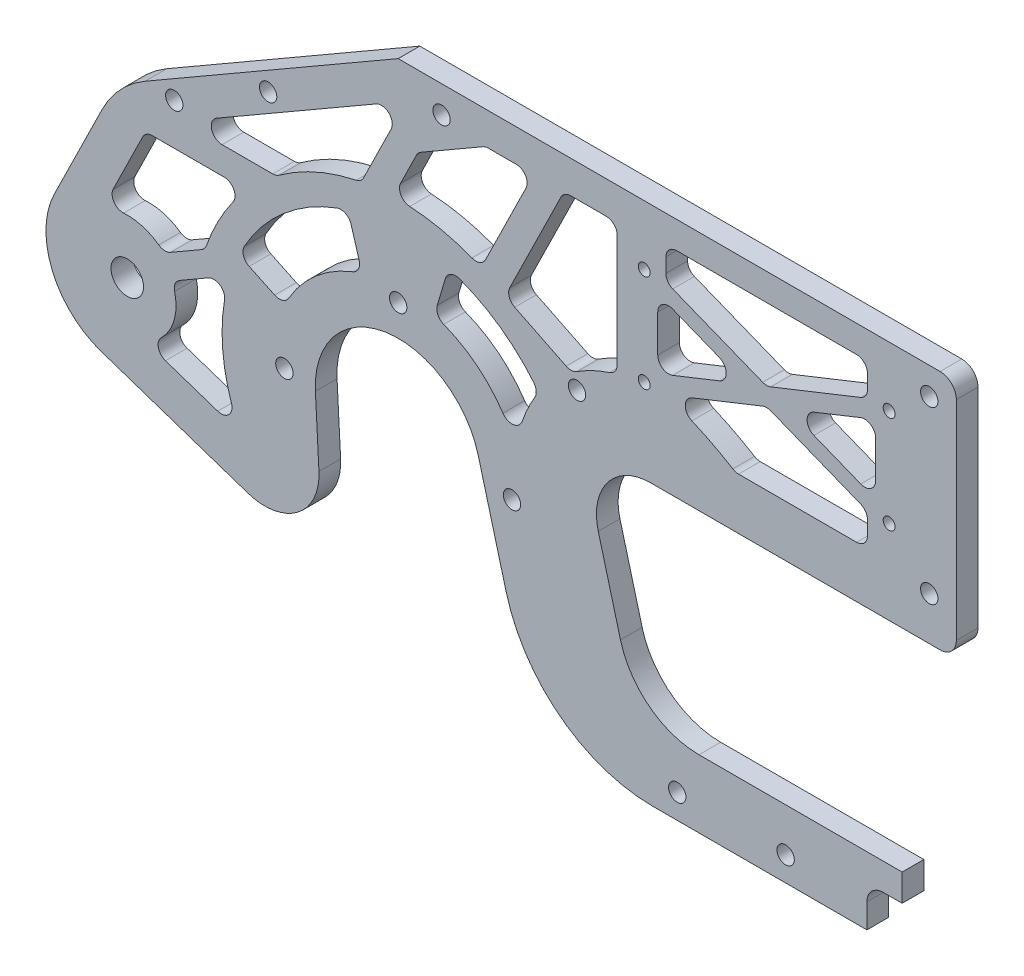
SolidWorks part; units mm, degrees
material "环氧树脂FR-4"
ref_plane "前视基准面" through (0, 0, 0) normal (0, 0, 1) x (1, 0, 0)
ref_plane "上视基准面" through (0, 0, 0) normal (0, 1, 0) x (1, 0, 0)
ref_plane "右视基准面" through (0, 0, 0) normal (1, 0, 0) x (0, 0, -1)
sketch "草图1" plane through (0, 0, 0) normal (0, 0, 1) x (1, 0, 0)
  line L1 (0, 60) -> (103, 60)
  line L2 (103, 60) -> (103, 15.5)
  line L3 (103, 15.5) -> (33.55, 15.5)
  line L4 (33.55, 15.5) -> (44, -23.5)
  line L5 (44, -23.5) -> (93, -23.5)
  line L6 (93, -23.5) -> (93, -36)
  line L7 (93, -36) -> (10, -36)
  line L9 (-50, 0) -> (0, 0) construction
  line L10 (0, 60) -> (-51.9615, 30)
  line L11 (10, -36) -> (-54.7807, -14.2178)
  line L12 (-51.9615, 30) -> (-63.4602, 6.6199)
  circle A0 centre (0, 0) radius 15.3
  circle A1 centre (0, 0) radius 20 construction
  circle A2 centre (-50, 0) radius 3
  circle A3 centre (-50, 0) radius 15
  dimension "D1" = 30.6
  dimension "D2" = 40
  dimension "D13" = 50
  dimension "D14" = 6
  dimension "D8" = 93
  dimension "D6" = 30
  dimension "D3" = 36
  dimension "D4" = 105
  dimension "D5" = 44.5
  dimension "D7" = 10
  dimension "D9" = 39
  dimension "D10" = 153
  dimension "D11" = 0
  dimension "D12" = 60
  dimension "D16" = 44
  dimension "D17" = 30
  dimension "D18" = 30
extrude "凸台-拉伸1" add sketch "草图1" along normal blind 4 contours A3 L11 L7 L6 L5 L4 L3 L2 L1 A0 | A3 A2 region at (25.8343, 17.652, 0) region at (-46.6978, 14.1967, 0)
sketch "草图4" plane through (0, 0, 0) normal (0, 0, 1) x (1, 0, 0)
  circle A0 centre (0, 0) radius 34
  dimension "D1" = 68
sketch "草图2" plane through (0, 0, 0) normal (0, 0, 1) x (1, 0, 0)
  line L0 (0, 0) -> (0, 21) construction
  circle A0 centre (0, 21) radius 1.6
  circle A1 centre (21, 0) radius 1.6
  circle A2 centre (0, -21) radius 1.6
  circle A3 centre (-21, 0) radius 1.6
  dimension "D3" = 3.2
  dimension "D2" = 21
  dimension "D1" = 4
extrude "切除-拉伸1" cut sketch "草图2" along normal through all
fillet "圆角1" radius 10 1 edges at (33.55, 15.5, 2)
fillet "圆角2" radius 15 1 edges at (44, -23.5, 2)
sketch "草图3" plane through (0, 0, 0) normal (0, 0, 1) x (1, 0, 0)
  line L1 (90.6, 31) -> (45.4, 31) construction
  line L2 (90.6, 31) -> (90.6, 49) construction
  line L3 (90.6, 49) -> (45.4, 49) construction
  line L4 (45.4, 31) -> (45.4, 49) construction
  line L5 (90.6, 31) -> (45.4, 49) construction
  line L6 (90.6, 49) -> (45.4, 31) construction
  circle A0 centre (90.6, 49) radius 1.1
  circle A1 centre (45.4, 49) radius 1.1
  circle A2 centre (45.4, 31) radius 1.1
  circle A3 centre (90.6, 31) radius 1.1
  point P0 (68, 40)
  dimension "D5" = 2.2
  dimension "D1" = 45.2
  dimension "D2" = 18
  dimension "D3" = 40
  dimension "D4" = 68
extrude "切除-拉伸2" cut sketch "草图3" along normal through all
sketch "草图5" plane through (0, 0, 4) normal (0, 0, 1) x (1, 0, 0)
  line L0 (10, -36) -> (-54.7807, -14.2178) construction
  circle A0 centre (-35, -20.8689) radius 12.5
  circle A1 centre (-50, 0) radius 3 construction
  dimension "D1" = 15
  dimension "D2" = 25
extrude "切除-拉伸3" [suppressed] cut sketch "草图5" against normal through all
sketch "草图7" plane through (0, 0, 4) normal (0, 0, 1) x (1, 0, 0)
  line L1 (14.7787, 3.9599) -> (25.4859, -36)
  line L5 (93, -36) -> (10, -36) construction
  line L6 (36.923, 2.9118) -> (41.021, -12.3823) construction
  line L8 (10, -36) -> (-54.7807, -14.2178) construction
  line L9 (14.7787, 3.9599) -> (-14.7787, -3.9599) construction
  line L11 (-13.8547, -27.979) -> (10, -36)
  line L12 (10, -36) -> (25.4859, -36)
  line L13 (-13.8547, -27.979) -> (-15.279, -0.8007)
  line L14 (-15.279, -0.8007) -> (14.7787, 3.9599)
  circle A0 centre (0, 0) radius 15.3 construction
  circle A1 centre (0, 0) radius 15.3 construction
  dimension "D1" = 12
extrude "切除-拉伸4" cut sketch "草图7" against normal through all
sketch "草图8" plane through (0, 0, 4) normal (0, 0, 1) x (1, 0, 0)
  line L0 (51.5, -31.5) -> (71.5, -31.5) construction
  line L3 (93, -23.5) -> (93, -36) construction
  line L9 (55.5099, -23.5) -> (93, -23.5) construction
  circle A4 centre (71.5, -31.5) radius 1.6
  circle A5 centre (51.5, -31.5) radius 1.6
  dimension "D1" = 8
  dimension "D2" = 3.2
  dimension "D3" = 21.5
  dimension "D4" = 20
extrude "切除-拉伸7" cut sketch "草图8" against normal through all
sketch "草图10" plane through (0, 0, 4) normal (0, 0, 1) x (1, 0, 0)
  line L0 (93, -28.5) -> (86.5, -28.5)
  line L1 (93, -23.5) -> (93, -36) construction
  line L2 (86.5, -28.5) -> (86.5, -36)
  line L3 (93, -36) -> (25.4859, -36) construction
  line L4 (86.5, -36) -> (93, -36)
  line L5 (93, -36) -> (93, -28.5)
  line L6 (55.5099, -23.5) -> (93, -23.5) construction
  dimension "D1" = 5
  dimension "D2" = 6.5
extrude "切除-拉伸8" cut sketch "草图10" against normal through all
sketch "草图17" plane through (0, 0, 0) normal (0, 0, -1) x (-1, 0, 0)
  line L0 (-103, 60) -> (-103, 15.5) construction
  line L1 (-103, 15.5) -> (-46.5822, 15.5) construction
  line L2 (0, 60) -> (-103, 60) construction
  circle A0 centre (-98, 23.5) radius 1.6
  circle A1 centre (-98, 55) radius 1.6
  circle A2 centre (-33, 23.5) radius 1.6
  circle A3 centre (-8, 55) radius 1.6
  dimension "D1" = 5
  dimension "D3" = 3.2
  dimension "D4" = 5
  dimension "D5" = 65
  dimension "D6" = 90
  dimension "D2" = 8
extrude "切除-拉伸14" cut sketch "草图17" against normal through all
fillet "圆角3" radius 3 1 edges at (86.5, -28.5, 2)
sketch "草图11" plane through (0, 0, 0) normal (0, 0, -1) x (-1, 0, 0)
  line L0 (-21.9089, -7) -> (-31.2966, -7)
  line L1 (-31.2966, -7) -> (-37.4595, -30)
  line L2 (-37.4595, -30) -> (-10, -30)
  line L3 (-10, -30) -> (-3.2852, -27.7422)
  line L4 (13.8547, -27.979) -> (54.7807, -14.2178) construction
  line L5 (-86.5, -36) -> (-25.4859, -36) construction
  line L6 (-36.923, 2.9118) -> (-41.021, -12.3823) construction
  line L7 (16, -19.8725) -> (43.4459, -10.6439)
  line L8 (16, -19.8725) -> (16, -16.5227)
  line L9 (28.5, 0) -> (37.5, 0)
  line L10 (47.3524, 28.0423) -> (-7.1185, 59.4911)
  line L11 (-7.1185, 59.4911) -> (-7.1185, 21.8707)
  line L12 (47.3524, 28.0423) -> (55.6635, 11.1434)
  line L13 (31.7893, 37.0277) -> (44.4834, 11.2168)
  line L14 (44.4834, 11.2168) -> (20.0794, 11.2168)
  line L15 (0, 60) -> (51.9615, 30) construction
  line L16 (26.3422, 40.1725) -> (40.583, 11.2168)
  line L17 (12.3354, 48.2594) -> (30.5534, 11.2168)
  line L18 (6.8883, 51.4042) -> (26.653, 11.2168)
  line L19 (-7.1185, 59.4911) -> (11.843, 20.9369)
  line L20 (50, 12.5) -> (4.9656, 22.4576)
  line L21 (51.9615, 30) -> (63.4602, 6.6199) construction
  line L22 (-20.0278, -11.3087) -> (-25.0361, -30)
  line L23 (-17.0059, -15.4855) -> (-20.895, -30)
  circle A0 centre (0, 0) radius 23
  circle A1 centre (0, -21) radius 7.5
  circle A2 centre (50, 0) radius 12.5
  circle A3 centre (21, 0) radius 7.5
  point P30 (0, -21)
  dimension "D1" = 15
  dimension "D5" = 25
  dimension "D8" = 46
  dimension "D2" = 6
  dimension "D3" = 8
  dimension "D4" = 7
  dimension "D6" = 7
  dimension "D7" = 16
  dimension "D9" = 4
  dimension "D10" = 5
  dimension "D11" = 3.5
  dimension "D12" = 3.5
  dimension "D13" = 9
  dimension "D14" = 9
  dimension "D15" = 12
  dimension "D16" = 4
extrude "切除-拉伸9" [suppressed] cut sketch "草图11" against normal through all contours A3 A0 L8 L7 A2 L9 | A2 L12 L10 L13 L20 | L20 L16 L10 L17 | L20 L18 L10 L19 | A0 L0 L1 L2 L22 | A1 A0 L23 L2 L3
fillet "圆角4" [suppressed] radius 3
sketch "草图12" [suppressed] plane through (0, 0, 0) normal (0, 0, -1) x (-1, 0, 0)
  line L0 (-4.0881, 42) -> (-10.4817, 55)
  line L1 (-10.4817, 55) -> (-28.4817, 55)
  line L2 (-28.4817, 55) -> (-22.0881, 42)
  line L3 (-22.0881, 42) -> (-4.0881, 42)
  line L4 (0, 60) -> (-103, 60) construction
  line L7 (-2.7623, 50.6337) -> (11.843, 20.9369) construction
  line L8 (-14.2191, 26) -> (3.7809, 26)
  line L9 (3.7809, 26) -> (-2.6127, 39)
  line L10 (-2.6127, 39) -> (-20.6127, 39)
  line L11 (-20.6127, 39) -> (-14.2191, 26)
  dimension "D6" = 3
  dimension "D1" = 5
  dimension "D2" = 5
  dimension "D3" = 18
  dimension "D4" = 13
  dimension "D5" = 2
extrude "切除-拉伸10" [suppressed] cut sketch "草图12" against normal blind 10 contours L2 L3 L0 L1 | L10 L11 L8 L9 | L8 L9 L10 L11
sketch "草图14" plane through (0, 0, 0) normal (0, 0, -1) x (-1, 0, 0)
  line L0 (0, 60) -> (-103, 60) construction
  line L1 (-103, 60) -> (-103, 15.5) construction
  circle A0 centre (-98, 55) radius 1.6
  circle A1 centre (-6, 55) radius 1.6
  dimension "D1" = 3.2
  dimension "D2" = 5
  dimension "D4" = 5
  dimension "D5" = 92
  dimension "D3" = 5
extrude "切除-拉伸11" [suppressed] cut sketch "草图14" against normal through all
chamfer "倒角1" [suppressed] distance 8 angle 45
sketch "草图15" [suppressed] plane through (0, 0, 0) normal (0, 0, -1) x (-1, 0, 0)
  line L0 (-26.1097, 7) -> (-21.9089, 7)
  line L1 (-15.404, 17.0797) -> (-22.2502, 31)
  line L2 (-22.2502, 31) -> (-40.4, 31)
  line L3 (-45.4, 31) -> (-42.7797, 25.6721)
  line L4 (-20.6127, 39) -> (-14.2191, 26) construction
  line L6 (-22.2502, 31) -> (-37.0907, 23.7012)
  circle A1 centre (0, 0) radius 23
  circle A2 centre (-46.5822, 5.5) radius 20.5274
  circle A4 centre (-45.4, 31) radius 5
  circle A5 centre (-21, 0) radius 1.6 construction
  dimension "D2" = 10
  dimension "D4" = 46
  dimension "D5" = 7
  dimension "D3" = 5
extrude "切除-拉伸12" [suppressed] cut sketch "草图15" against normal through all contours A4 L3 A2 L0 A1 L1 L2
sketch "草图16" plane through (0, 0, 0) normal (0, 0, -1) x (-1, 0, 0)
  line L0 (-1.6077, 54) -> (39.9615, 30)
  line L2 (22.5, 30) -> (39.9615, 30)
  line L3 (0, 0) -> (9.2857, 31.1452)
  line L4 (0, 60) -> (51.9615, 30) construction
  line L5 (0, 0) -> (29.364, 13.9286)
  line L6 (27.9508, 25) -> (46.6198, 25)
  line L7 (46.6198, 25) -> (54.5308, 8.9147)
  line L8 (51.9615, 30) -> (63.4602, 6.6199) construction
  line L9 (43.209, 7.3405) -> (35.6211, 11.7214)
  line L10 (-1.6077, 54) -> (6.8143, 36.8757)
  line L11 (-30.582, 54) -> (-19.7132, 31.9005)
  line L12 (-7.1797, 54) -> (0.9411, 37.4882)
  line L13 (-7.1797, 54) -> (-25.01, 54)
  line L14 (-25.01, 54) -> (-15.292, 34.2404)
  line L15 (0, 60) -> (-103, 60) construction
  line L24 (-30.582, 54) -> (-40.4, 54)
  line L25 (-40.4, 54) -> (-40.4, 29.7235)
  line L26 (0, 21) -> (0, -0.6458) construction
  line L27 (-90.6, 49) -> (-45.4, 49) construction
  line L28 (-45.4, 49) -> (-45.4, 31) construction
  line L29 (-45.4, 31) -> (-90.6, 31) construction
  line L30 (-90.6, 31) -> (-90.6, 49) construction
  line L31 (-90.6, 40) -> (-45.4, 40) construction
  line L32 (-88.1, 46.3899) -> (-72.0544, 40)
  line L33 (-88.1, 46.3899) -> (-88.1, 33.6101)
  line L34 (-68, 49) -> (-68, 31) construction
  line L35 (-90.6, 49) -> (-68, 40) construction
  line L36 (-88.1, 33.6101) -> (-72.0544, 40)
  line L37 (-47.9, 46.3899) -> (-47.9, 33.6101)
  line L38 (-47.9, 46.3899) -> (-63.9456, 40)
  line L39 (-47.9, 33.6101) -> (-63.9456, 40)
  line L40 (-86.6, 49.0216) -> (-68, 41.6146)
  line L41 (-68, 41.6146) -> (-49.4, 49.0216)
  line L44 (-68, 38.3854) -> (-49.4, 30.9784)
  line L45 (-86.6, 30.9784) -> (-68, 38.3854)
  line L46 (0, 0) -> (-21.0517, 9.9857)
  line L47 (0, 0) -> (-9.2857, 31.1452)
  line L48 (-22.0821, 10.4745) -> (-29.364, 13.9286)
  line L50 (-19.7132, 31.9005) -> (-32.0422, 25.8369)
  line L51 (-86.6, 49.0216) -> (-86.6, 55)
  line L52 (-86.6, 55) -> (-49.4, 55)
  line L53 (-49.4, 55) -> (-49.4, 49.0216)
  line L54 (-49.4, 25) -> (-49.4, 30.9784)
  line L55 (-86.6, 25) -> (-49.4, 25)
  line L56 (-86.6, 30.9784) -> (-86.6, 25)
  line L57 (-16.0949, 54) -> (-3.6444, 46.8117)
  circle A0 centre (0, 0) radius 23.3
  circle A1 centre (0, 0) radius 37.5
  circle A2 centre (50, 0) radius 10
  arc A3 (15.279, -0.8007) -> (-14.7787, 3.9599) centre (0, 0) ccw construction
  circle A4 centre (0, 0) radius 32.5
  circle A5 centre (0, 21) radius 1.6 construction
  circle A6 centre (21, 0) radius 1.6 construction
  arc A7 (-62.2267, 25) -> (-49.4, 30.3407) centre (-46.5822, 5.5) ccw
  circle A8 centre (-45.4, 49) radius 1.1 construction
  circle A10 centre (-90.6, 49) radius 1.1 construction
  arc A11 (-49.4, 30.9784) -> (-62.2267, 25) centre (-32.7715, -21.4477) ccw
  point P59 (-88.1, 40)
  dimension "D1" = 8
  dimension "D3" = 75
  dimension "D4" = 20
  dimension "D8" = 5
  dimension "D14" = 50
  dimension "D15" = 1.5
  dimension "D23" = 4
  dimension "D25" = 55
  dimension "D2" = 6
  dimension "D5" = 5
  dimension "D6" = 7
  dimension "D7" = 24
  dimension "D9" = 6
  dimension "D10" = 9
  dimension "D11" = 6
  dimension "D12" = 6
  dimension "D13" = 5
  dimension "D16" = 2.5
  dimension "D17" = 1.5
  dimension "D18" = 4
  dimension "D19" = 5
  dimension "D20" = 16
  dimension "D21" = 5
  dimension "D22" = 90
  dimension "D24" = 5
extrude "切除-拉伸13" cut sketch "草图16" against normal through all contours L29 L27 | L33 L36 L32 | L45 L44 | L41 L40 | L39 L37 L38 | L11 L24 L25 | A1 L12 L13 L14 | A1 L2 L0 L10 | A2 L7 L6 A1 L9 | L5 A4 L3 A0 | A7 A0 L47 A4 region at (-16.6542, 38.9523, 0) region at (12.3908, 44.4606, 0) region at (-41.6889, 17.2049, 0) region at (32.2752, 39.6319, 0) region at (16.5231, 21.6807, 0) region at (69.8944, 30.4756, 0) region at (-17.794, 20.7516, 0) region at (82.7515, 40, 0) region at (53.2485, 40, 0) region at (68, 49.9229, 0)
fillet "圆角5" radius 10 1 edges at (-13.8547, -27.979, 2)
fillet "圆角6" radius 28 1 edges at (25.4859, -36, 2)
fillet "圆角7" radius 2 43 edges at (1.6077, 54, 2) (-39.9615, 30, 2) (-22.5, 30, 2) (-6.8143, 36.8757, 2) (-35.6211, 11.7214, 2) (-27.9508, 25, 2) (-46.6198, 25, 2) (-54.5308, 8.9147, 2) (-43.209, 7.3405, 2) (9.2857, 31.1452, 2) (6.6571, 22.3287, 2) (25.9316, 19.5908, 2) (40.4, 54, 2) (30.582, 54, 2) (40.4, 29.7235, 2) (25.01, 54, 2) (-0.9411, 37.4882, 2) (15.292, 34.2404, 2) (47.9, 46.3899, 2) (47.9, 33.6101, 2) (63.9456, 40, 2) (68, 38.3854, 2) (88.1, 46.3899, 2) (72.0544, 40, 2) (88.1, 33.6101, 2) (68, 41.6146, 2) (-21.0517, 9.9857, 2) (-6.6571, 22.3287, 2) (-9.2857, 31.1452, 2) (-29.364, 13.9286, 2) (21.7469, 8.3644, 2) (32.0422, 25.8369, 2) (86.6, 25, 2) (86.6, 30.9784, 2) (62.2267, 25, 2) (86.6, 49.0216, 2) (86.6, 55, 2) (49.4, 55, 2) (49.4, 49.0216, 2) (19.7132, 31.9005, 2) (49.4, 30.9784, 2) (3.6444, 46.8117, 2) (16.0949, 54, 2)
sketch "草图18" plane through (0, 0, 0) normal (0, 0, -1) x (-1, 0, 0)
  line L0 (30.9958, 9.773) -> (41.7386, 3.5706)
  line L1 (29.1353, -14.4008) -> (46.8691, -8.4379)
  line L2 (27.798, -23.2906) -> (54.7807, -14.2178) construction
  line L3 (42.0183, 8.0279) -> (36.2724, 11.3453) construction
  circle A0 centre (0, 0) radius 32.5
  circle A1 centre (0, 0) radius 23
  circle A2 centre (50, 0) radius 9
  dimension "D1" = 46
  dimension "D2" = 65
  dimension "D3" = 18
  dimension "D4" = 4
  dimension "D5" = 8
extrude "切除-拉伸15" cut sketch "草图18" against normal blind 10 contours A2 L0 A0 L1 region at (-36.6475, -3.4342, 0)
fillet "圆角8" radius 2 4 edges at (-29.1353, -14.4008, 2) (-41.7386, 3.5706, 2) (-46.8691, -8.4379, 2) (-30.9958, 9.773, 2)
fillet "圆角9" radius 3 2 edges at (103, 60, 2) (103, 15.5, 2)
fillet "圆角10" radius 20 1 edges at (-51.9615, 30, 2)
sketch "草图20" plane through (0, 0, 0) normal (0, 0, -1) x (-1, 0, 0)
  line L0 (24, 42.6795) -> (41.3205, 32.6795) construction
  line L1 (0, 60) -> (46.6973, 33.0393) construction
  circle A0 centre (24, 42.6795) radius 1.6
  circle A1 centre (41.3205, 32.6795) radius 1.6
  dimension "D2" = 3.2
  dimension "D4" = 24
  dimension "D1" = 3
  dimension "D3" = 20
extrude "切除-拉伸16" cut sketch "草图20" against normal through all
